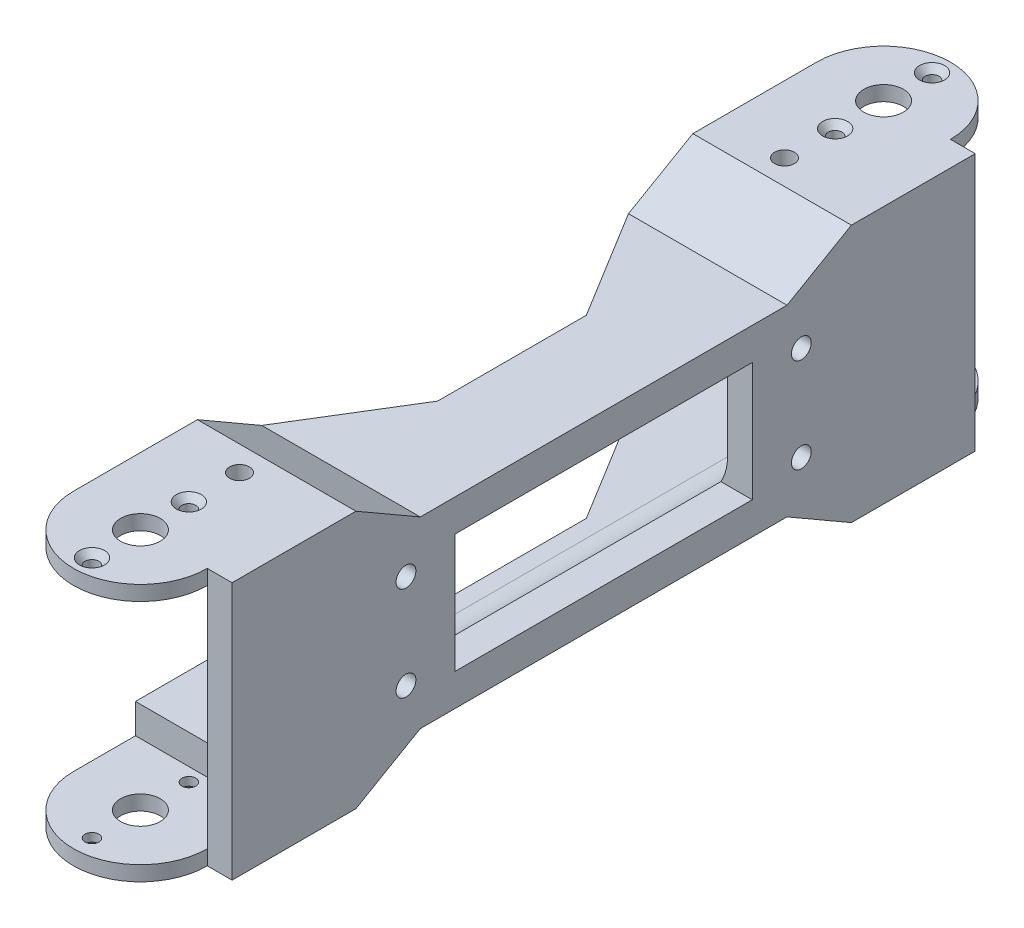
SolidWorks part; units mm, degrees
material "POM Acetal Copolymer"
ref_plane "Front Plane" through (0, 0, 0) normal (0, 0, 1) x (1, 0, 0)
ref_plane "Top Plane" through (0, 0, 0) normal (0, 1, 0) x (1, 0, 0)
ref_plane "Right Plane" through (0, 0, 0) normal (1, 0, 0) x (0, 0, -1)
sketch "Sketch1" plane through (0, 0, 0) normal (0, 1, 0) x (1, 0, 0)
  line L0 (0, 75) -> (0, -75) construction
  line L2 (-13.5, 75) -> (-13.5, -75)
  line L4 (13.5, 75) -> (13.5, -75)
  arc A0 (13.5, 75) -> (-13.5, 75) centre (0, 75) ccw
  arc A1 (-13.5, -75) -> (13.5, -75) centre (0, -75) ccw
  circle A2 centre (0, -55) radius 2
  point P5 (0, 0)
  dimension "D3" = 4
  dimension "D1" = 150
  dimension "D2" = 27
  dimension "D4" = 20
extrude "Boss-Extrude1" add sketch "Sketch1" along normal mid plane 52
sketch "Sketch3" plane through (-13.5, 0, 0) normal (-1, 0, 0) x (0, 0, 1)
  line L0 (-50, 26) -> (-37.0096, 18.5)
  line L1 (-75, 26) -> (75, 26) construction
  line L2 (-37.0096, 18.5) -> (37.0096, 18.5)
  line L3 (37.0096, 18.5) -> (50, 26)
  line L4 (50, 26) -> (-50, 26)
  line L5 (-75, 26) -> (-75, -26) construction
  point P6 (0, 18.5)
  point P7 (0, 26)
  dimension "D1" = 7.5
  dimension "D2" = 30
  dimension "D3" = 25
extrude "Cut-Extrude1" cut sketch "Sketch3" against normal through all both and the other way through all
mirror "Mirror1" about plane through (0, 0, 0) normal (0, 1, 0) of "Cut-Extrude1"
sketch "Sketch4" plane through (-13.5, 0, 0) normal (-1, 0, 0) x (0, 0, 1)
  line L0 (-88.5, 26) -> (-88.5, -26) construction
  line L1 (62.5, 23) -> (88.5, 23)
  line L2 (-88.5, 23) -> (-62.5, 23)
  line L3 (-88.5, 23) -> (-88.5, 17)
  line L4 (-88.5, 17) -> (-62.5, 17)
  line L5 (-62.5, 23) -> (-62.5, 17)
  line L6 (-88.5, -23) -> (-62.5, -23)
  line L7 (-88.5, -23) -> (-88.5, -17)
  line L8 (-88.5, -17) -> (-62.5, -17)
  line L9 (-62.5, -23) -> (-62.5, -17)
  line L10 (62.5, 23) -> (62.5, 17)
  line L11 (62.5, 17) -> (88.5, 17)
  line L12 (88.5, 23) -> (88.5, 17)
  line L13 (62.5, -17) -> (88.5, -17)
  line L14 (62.5, -17) -> (62.5, -23)
  line L15 (62.5, -23) -> (88.5, -23)
  line L16 (88.5, -17) -> (88.5, -23)
  line L18 (88.5, -26) -> (88.5, 26) construction
  line L19 (-62.5, 17) -> (-62.5, -17) construction
  line L20 (62.5, 17) -> (62.5, -17) construction
  point P20 (-62.5, 0)
  dimension "D1" = 26
  dimension "D2" = 6
  dimension "D3" = 34
extrude "Cut-Extrude2" cut sketch "Sketch4" against normal through all both
sketch "Sketch5" plane through (-13.5, 0, 0) normal (-1, 0, 0) x (0, 0, 1)
  line L1 (-88.5, 17) -> (88.5, 17)
  line L2 (-88.5, 17) -> (-88.5, -17)
  line L3 (-88.5, -17) -> (88.5, -17)
  line L4 (88.5, 17) -> (88.5, -17)
extrude "Cut-Extrude3" cut sketch "Sketch5" against normal offset from surface (22 mm away) 5 up to face at (13.5, 0, 0)
sketch "Sketch6" plane through (8.5, 0, 0) normal (-1, 0, 0) x (0, 0, 1)
  line L0 (62.5, -17) -> (-62.5, -17) construction
  line L1 (85.4881, 17) -> (62.5, 17)
  line L2 (85.4881, 17) -> (85.4881, -17)
  line L3 (85.4881, -17) -> (62.5, -17)
  line L4 (62.5, 17) -> (62.5, -17)
  line L5 (62.5, -17) -> (62.5, -23) construction
extrude "Cut-Extrude4" cut sketch "Sketch6" against normal through all
sketch "Sketch7" plane through (8.5, 0, 0) normal (-1, 0, 0) x (0, 0, 1)
  line L1 (-85.4881, 17) -> (-62.5, 17)
  line L2 (-85.4881, 17) -> (-85.4881, -17)
  line L3 (-85.4881, -17) -> (-62.5, -17)
  line L4 (-62.5, 17) -> (-62.5, -17)
extrude "Cut-Extrude5" cut sketch "Sketch7" against normal through all
hole_wizard "CSK for #3 Flat Head Machine Screw1" positions "Sketch11" profile "Sketch12" countersink size "#3" standard "ANSI Inch"
sketch "Sketch11" plane through (0, 26, 0) normal (0, 1, 0) x (1, 0, 0)
  line L0 (9.779, -75) -> (-9.779, -75) construction
  line L2 (0, -65.221) -> (0, -84.779) construction
  arc A0 (-13.5, -75) -> (13.5, -75) centre (0, -75) ccw construction
  point P0 (0, -65.221)
  point P6 (0, -84.779)
  point P17 (0, -75)
  point P18 (0, -75)
  dimension "D1" = 19.558
sketch "Sketch12" plane through (0, 26, 65.221) normal (1, 0, 0) x (0, 0, 1)
  line L0 (0, 0) -> (0, 3.8394)
  line L1 (0, 3.8394) -> (1.397, 3)
  line L2 (1.397, 3) -> (1.397, 1.3003)
  line L3 (1.397, 1.3003) -> (2.5273, 0)
  line L5 (2.5273, 0) -> (0, 0)
  line L6 (-1.397, 1.3003) -> (-2.5273, 0) construction
  line L10 (0, 3.8394) -> (-1.397, 3) construction
  line L11 (0, -6.35) -> (0, 107.95) construction
  dimension "Hole Dia." = 2.794
  dimension "Hole Depth" = 3
  dimension "Near C'Sink Dia." = 5.0546
  dimension "Near C'Sink Angle" = 82
  dimension "Drill Angle" = 118
mirror "Mirror5" about plane through (0, 0, 0) normal (0, 1, 0) of "CSK for #3 Flat Head Machine Screw1"
mirror "Mirror3" about plane through (0, 0, 0) normal (0, 0, 1) of "CSK for #3 Flat Head Machine Screw1"
sketch "Sketch13" plane through (0, -26, 0) normal (0, -1, 0) x (1, 0, 0)
  circle A0 centre (0, -75) radius 4
  arc A1 (-13.5, -75) -> (13.5, -75) centre (0, -75) ccw construction
  dimension "D1" = 8
extrude "Cut-Extrude6" cut sketch "Sketch13" against normal through all both and the other way through all
mirror "Mirror4" about plane through (0, 0, 0) normal (0, 0, 1) of "Cut-Extrude6"
sketch "Sketch14" plane through (13.5, 0, 0) normal (1, 0, 0) x (0, 0, -1)
  line L0 (-75, 26) -> (-75, 23)
  line L1 (-75, 23) -> (-62.5, 23)
  line L2 (-62.5, 23) -> (-62.5, -23)
  line L3 (-62.5, -23) -> (-75, -23)
  line L4 (-75, -23) -> (-75, -26)
  line L5 (-75, -26) -> (-50, -26)
  line L6 (-50, -26) -> (-37.0096, -18.5)
  line L7 (-37.0096, -18.5) -> (37.0096, -18.5)
  line L8 (37.0096, -18.5) -> (50, -26)
  line L12 (62.5, -23) -> (62.5, 23)
  line L13 (62.5, 23) -> (75, 23)
  line L14 (75, 23) -> (75, 26)
  line L15 (75, 26) -> (50, 26)
  line L16 (50, 26) -> (37.0096, 18.5)
  line L17 (37.0096, 18.5) -> (-37.0096, 18.5)
  line L18 (-37.0096, 18.5) -> (-50, 26)
  line L19 (-50, 26) -> (-75, 26)
  line L20 (62.5, -23) -> (75, -23)
  line L21 (75, -23) -> (75, -26)
  line L22 (75, -26) -> (50, -26)
extrude "Boss-Extrude2" add sketch "Sketch14" along normal blind 5
sketch "Sketch15" plane through (8.5, 0, 0) normal (-1, 0, 0) x (0, 0, 1)
  line L1 (-62.5, 17) -> (62.5, 17)
  line L2 (-62.5, 17) -> (-62.5, -17)
  line L3 (-62.5, -17) -> (62.5, -17)
  line L4 (62.5, 17) -> (62.5, -17)
extrude "Cut-Extrude7" cut sketch "Sketch15" against normal blind 5
sketch "Sketch17" plane through (0, 0, 62.5) normal (0, 0, 1) x (1, 0, 0)
  line L0 (18.5, -26) -> (13.5, -26) construction
  line L1 (18.5, 26) -> (13.5, 26)
  line L2 (18.5, 26) -> (18.5, -26)
  line L3 (18.5, -26) -> (13.5, -26)
  line L4 (13.5, 26) -> (13.5, -26)
  line L5 (13.5, -17) -> (13.5, 17) construction
extrude "Boss-Extrude4" add sketch "Sketch17" along normal up to surface (12.5 mm away) up to face at (16, 24.5, 75)
mirror "Mirror6" about plane through (0, 0, 0) normal (0, 1, 0) of "Mirror3"
sketch "Sketch19" plane through (18.5, 0, 0) normal (1, 0, 0) x (0, 0, -1)
  line L0 (-39.899, 9.525) -> (-39.899, -9.525) construction
  line L3 (-75, 26) -> (-75, -26) construction
  circle A0 centre (-39.899, 9.525) radius 2
  circle A1 centre (-39.899, -9.525) radius 2
  point P4 (-39.899, 0)
  dimension "D2" = 4
  dimension "D1" = 19.05
  dimension "D3" = 35.101
extrude "Cut-Extrude11" cut sketch "Sketch19" against normal blind 10
sketch "Sketch18" plane through (0, 26, 0) normal (0, 1, 0) x (1, 0, 0)
  circle A0 centre (0, 55) radius 2
  circle A2 centre (0, 75) radius 4 construction
  dimension "D1" = 4
  dimension "D2" = 20
extrude "Cut-Extrude8" cut sketch "Sketch18" against normal up to surface (52 mm away) up to face at (0, -26, -67.7483)
sketch "Sketch20" plane through (13.5, 0, 0) normal (-1, 0, 0) x (0, 0, 1)
  line L1 (-30, 12) -> (30, 12)
  line L2 (-30, 12) -> (-30, -12)
  line L3 (-30, -12) -> (30, -12)
  line L4 (30, 12) -> (30, -12)
  point P4 (30, 0)
  point P8 (0, -12)
  dimension "D1" = 60
  dimension "D2" = 24
extrude "Cut-Extrude10" cut sketch "Sketch20" against normal blind 10
mirror "Mirror7" about plane through (0, 0, 0) normal (0, 0, 1) of "Cut-Extrude11"
sketch "Sketch21" plane through (0, 18.5, 0) normal (0, 1, 0) x (1, 0, 0)
  line L0 (-13.5, 37.0096) -> (0, 15)
  line L2 (0, 15) -> (0, -15)
  line L3 (0, -15) -> (-13.5, -37.0096)
  line L4 (-13.5, -37.0096) -> (-13.5, 37.0096)
  line L5 (18.5, 37.0096) -> (-13.5, 37.0096) construction
  point P4 (-13.5, 0)
  point P9 (0, 0)
  dimension "D1" = 30
extrude "Cut-Extrude12" cut sketch "Sketch21" against normal up to surface (37 mm away) up to face at (2.5, -18.5, 0)
sketch "Sketch22" plane through (0, 0, -62.5) normal (0, 0, -1) x (-1, 0, 0)
  line L1 (-18.5, 23) -> (-13.5, 23)
  line L2 (-18.5, 23) -> (-18.5, -23)
  line L3 (-18.5, -23) -> (-13.5, -23)
  line L4 (-13.5, 23) -> (-13.5, -23)
extrude "Boss-Extrude5" add sketch "Sketch22" along normal up to surface (12.5 mm away) up to face at (16, 24.5, -75)
fillet "Fillet1" radius 10 2 edges at (13.5, 17, 0) (13.5, -17, 0)
